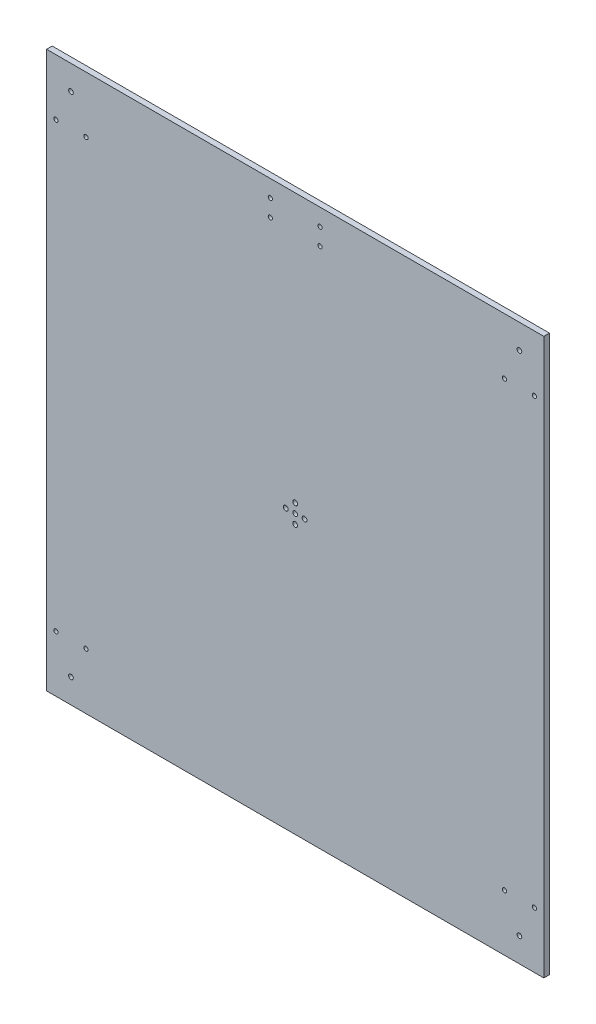
SolidWorks part; units mm, degrees
ref_plane "Спереди" through (0, 0, 0) normal (0, 0, 1) x (1, 0, 0)
ref_plane "Сверху" through (0, 0, 0) normal (0, 1, 0) x (1, 0, 0)
ref_plane "Справа" through (0, 0, 0) normal (1, 0, 0) x (0, 0, -1)
sketch "Эскиз3" plane through (0, 0, 0) normal (0, 0, 1) x (1, 0, 0)
  line L0 (0, 0) -> (0, 10) construction
  line L5 (265, -296.15) -> (-265, -296.15)
  line L6 (265, -296.15) -> (265, 296.15)
  line L7 (265, 296.15) -> (-265, 296.15)
  line L8 (-265, -296.15) -> (-265, 296.15)
  line L9 (0, 0) -> (10, 0) construction
  line L10 (0, 0) -> (0, -10) construction
  line L11 (0, 0) -> (-10, 0) construction
  circle A0 centre (0, 0) radius 2.55
  circle A1 centre (0, 10) radius 2.55
  circle A2 centre (10, 0) radius 2.55
  circle A3 centre (0, -10) radius 2.55
  circle A4 centre (-10, 0) radius 2.55
  point P0 (0, 0)
  point P5 (-265, 0)
  point P6 (0, 296.15)
  point P21 (0, 0)
  dimension "D3" = 5.1
  dimension "D4" = 5.1
  dimension "D1" = 592.3
  dimension "D2" = 530
  dimension "D5" = 10
  dimension "D6" = 4
extrude "Бобышка-Вытянуть1" add sketch "Эскиз3" along normal blind 6
sketch "Эскиз4" plane through (0, 0, 6) normal (0, 0, 1) x (1, 0, 0)
  line L0 (265, 296.15) -> (-265, 296.15) construction
  line L1 (-265, 296.15) -> (-265, -296.15) construction
  circle A0 centre (-239, 270.15) radius 2.5
  dimension "D1" = 5
  dimension "D2" = 26
  dimension "D3" = 26
extrude "Вырез-Вытянуть1" cut sketch "Эскиз4" against normal through all contours A0
pattern_linear "Линейный массив1" count 2 spacing 478 along (1, 0, 0) count 2 spacing 540.3 along (0, -1, 0) of "Вырез-Вытянуть1"
sketch "Эскиз7" plane through (0, 0, 0) normal (0, 0, -1) x (-1, 0, 0)
  line L9 (-26.5, 278.15) -> (26.5, 278.15) construction
  line L10 (-26.5, 278.15) -> (-26.5, 260.15) construction
  line L11 (-26.5, 260.15) -> (26.5, 260.15) construction
  line L16 (26.5, 278.15) -> (26.5, 260.15) construction
  line L17 (-265, 296.15) -> (265, 296.15) construction
  circle A0 centre (-26.5, 278.15) radius 2.25
  circle A1 centre (26.5, 278.15) radius 2.25
  circle A2 centre (-26.5, 260.15) radius 2.25
  circle A3 centre (26.5, 260.15) radius 2.25
  point P4 (0, 260.15)
  dimension "D4" = 4.5
  dimension "D5" = 4.5
  dimension "D6" = 4.5
  dimension "D7" = 4.5
  dimension "D1" = 53
  dimension "D2" = 18
  dimension "D3" = 18
extrude "Вырез-Вытянуть2" cut sketch "Эскиз7" against normal through all
sketch "Эскиз8" plane through (0, 0, 0) normal (0, 0, -1) x (-1, 0, 0)
  line L0 (223, 236.15) -> (255, 236.15) construction
  line L8 (265, 296.15) -> (265, -296.15) construction
  line L9 (-265, 296.15) -> (265, 296.15) construction
  circle A4 centre (223, 236.15) radius 2.25
  circle A5 centre (255, 236.15) radius 2.25
  dimension "D3" = 32
  dimension "D4" = 10
  dimension "D5" = 60
  dimension "D1" = 4.5
  dimension "D2" = 4.5
extrude "Вырез-Вытянуть3" cut sketch "Эскиз8" against normal through all
pattern_linear "Линейный массив2" count 2 spacing 472.3 along (0, -1, 0) count 2 spacing 478 along (1, 0, 0) of "Вырез-Вытянуть3"
equation "\"Ширина груза\"= 420"
equation "\"Глубина груза\"= 490"
equation "\"Высота груза\"= 297"
equation "\"Ширина ячейки\"= \"Ширина груза\" + 10"
equation "\"Глубина ячейки\"= \"Глубина груза\" + 10"
equation "\"Высота ячейки\"= \"Высота груза\" + 10 + 13"
equation "\"Колво ячеек ширина\"= 2"
equation "\"Колво ячеек высота\"= 2"
equation "\"Толщина стенки\" = 6"
equation "\"Крепление дверцы\"= 5 "
equation "\"Ширина рейки\"= \"Толщина шестерни\""
equation "\"Высота рейки\"= 20"
equation "\"Высота пола\"= \"Толщина стенки\" * 2"
equation "\"Колво полозьев\"= 5"
equation "\"Отступ рейки\"= 20"
equation "\"Глубина каретки\"= \"Глубина ячейки\" + 30 + \"Мотор Y высота корпуса\" + 20"
equation "\"Длинна рейки\"= ( \"Ширина ячейки\" + \"Толщина стенки\" + \"Крепление дверцы\" ) * \"Колво ячеек ширина\" + \"Ширина ячейки выгрузки\" * \"Колво выгрузки\" + \"Толщина стенки\""
equation "\"Отступ шпильки\"= 26"
equation "\"Диаметр шпильки\"= 5"
equation "\"D1@Бобышка-Вытянуть1\" = \"Толщина стенки\""
equation "\"D1@Эскиз4\"= \"Диаметр шпильки\""
equation "\"D2@Эскиз4\"=\"Отступ шпильки\""
equation "\"D3@Эскиз4\"= \"Отступ шпильки\""
equation "\"D2@Эскиз3\"=\"Ширина ячейки\" + \"Ширина пластины\" * 2"
equation "\"D1@Эскиз3\"=\"Глубина каретки\" "
equation "\"D3@Линейный массив1\"=\"Ширина ячейки\"  +\"Ширина пластины\" *2 - \"Отступ шпильки\" * 2"
equation "\"D4@Линейный массив1\"=\"Глубина каретки\" + \"Ширина рейки\" * 2 - \"Отступ шпильки\" * 2 - \"Ширина рейки\" * 2"
equation "\"Длинна шпильки\"= ( \"Высота ячейки\" + \"Толщина стенки\" + \"Высота пола\" ) * \"Колво ячеек высота\" + ( \"Толщина стенки\" + \"Отступ рейки\" ) * 2 "
equation "\"Ширина пластины\"= 50  "
equation "\"Высота зона выгрузки\"= \"Высота ячейки\" * 2 + \"Толщина стенки\" * 2"
equation "\"Колво выгрузки\"= 1"
equation "\"Отступ крепления мотора фиксации\" = 30"
equation "\"Мотор X ширина корпуса\"= 42.3"
equation "\"Мотор X высота корпуса\"= 42.3"
equation "\"Мотор X длина корпуса\"= 40"
equation "\"Мотор X вылет вала\"= 19.8"
equation "\"Мотор Y ширина корпуса\"= 42.3"
equation "\"Мотор Y высота корпуса\"= 42.3"
equation "\"Мотор Y длина корпуса\"= 48"
equation "\"Мотор Y вылет вала\"= 30"
equation "\"Мотор Z ширина корпуса\"= 42"
equation "\"Мотор Z высота корпуса\"= 42"
equation "\"Мотор Z длина корпуса\"= 40"
equation "\"Мотор Z вылет вала\"= 23"
equation "\"Мотор диаметр вала ПРЕДВ\"= 5"
equation "\"Мотор шаг крепления ПРЕДВ\"= 31"
equation "\"Мотор диаметр отверстий ПРЕДВ\"= 3"
equation "\"Мотор глубина отверстий ПРЕДВ\"= 4.5"
equation "\"Мотор диаметр буртика ПРЕДВ\"= 22"
equation "\"Мотор высота буртика ПРЕДВ\"= 2"
equation "\"Мотор диаметр шкива ПРЕДВ\"= 16"
equation "\"Мотор длина шкива ПРЕДВ\"= 12"
equation "\"Мотор отступ шкива ПРЕДВ\"= 5"
equation "\"Мотор X шаг градусов\"= 1.8"
equation "\"Мотор Y шаг градусов\"= 1.8"
equation "\"Мотор Z шаг градусов\"= 1.8"
equation "\"Мотор Y диаметр ротора\"= 25.78"
equation "\"Толщина шестерни\"= 10"
equation "\"Ширина ячейки выгрузки\"= \"Ширина ячейки\" + \"Толщина стенки\" + \"Отступ крепления мотора фиксации\"*2"
equation "\"D3@Линейный массив2\"=592.3-60*2"
equation "\"D4@Линейный массив2\"=530 - 26*2"
